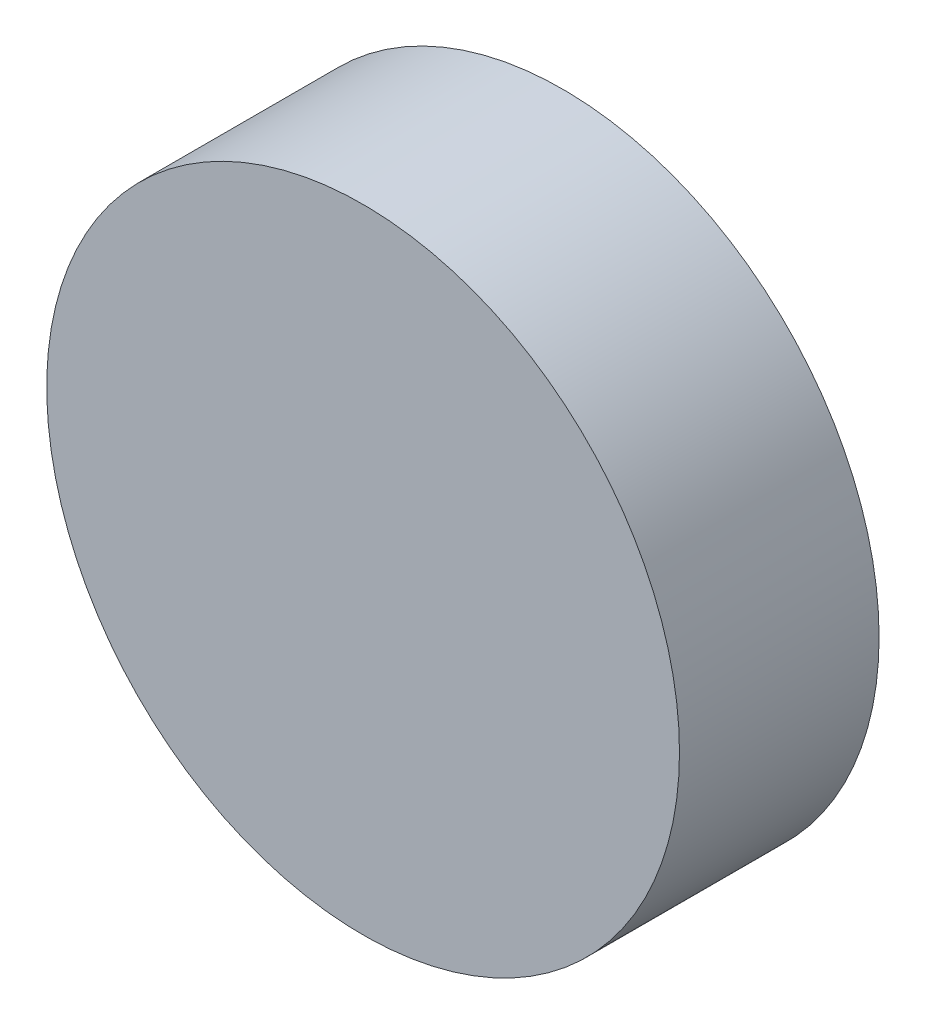
SolidWorks part; units mm, degrees
ref_plane "Front" through (0, 0, 0) normal (0, 0, 1) x (1, 0, 0)
ref_plane "Top" through (0, 0, 0) normal (0, 1, 0) x (1, 0, 0)
ref_plane "Right" through (0, 0, 0) normal (1, 0, 0) x (0, 0, -1)
sketch "Sketch1" plane through (0, 0, 0) normal (0, 0, 1) x (1, 0, 0)
  circle A0 centre (0, 0) radius 7.925
extrude "Extrude1" add sketch "Sketch1" along normal blind 5
